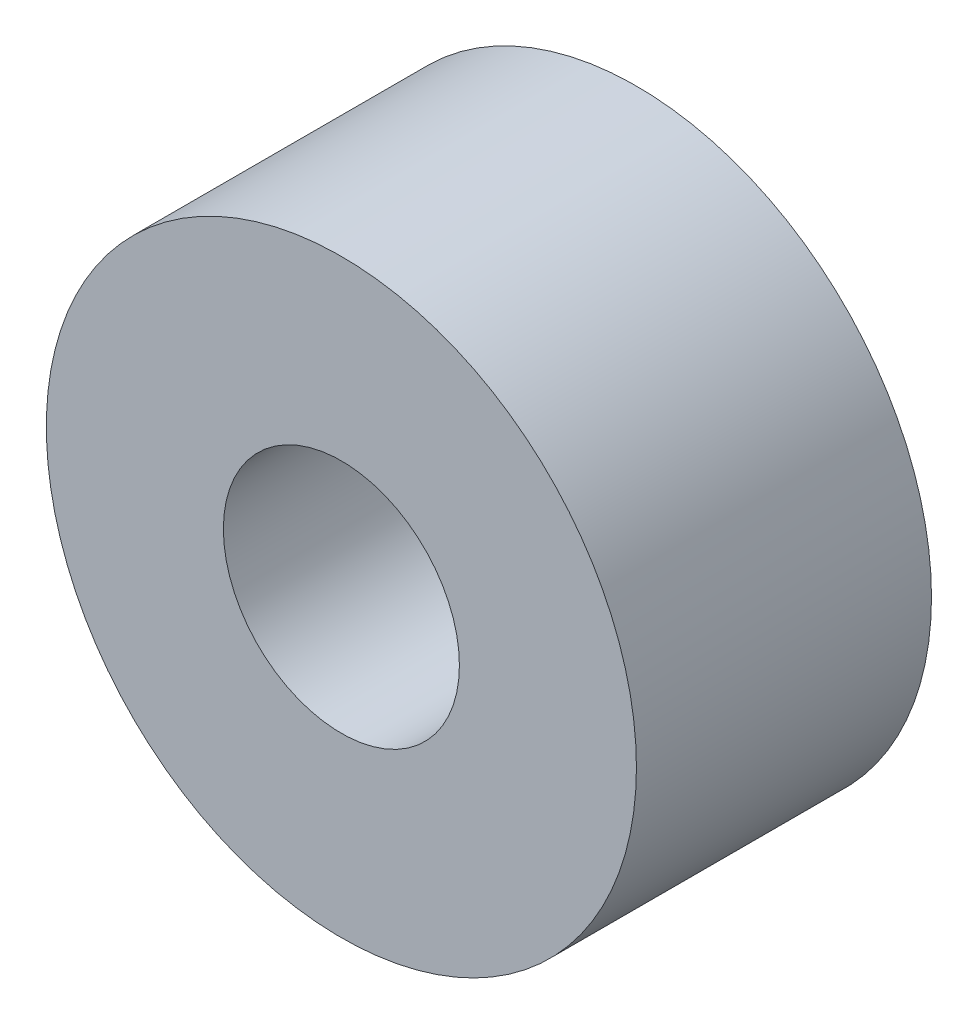
SolidWorks part; units mm, degrees
material "ABS"
ref_plane "Front Plane" through (0, 0, 0) normal (0, 0, 1) x (1, 0, 0)
ref_plane "Top Plane" through (0, 0, 0) normal (0, 1, 0) x (1, 0, 0)
ref_plane "Right Plane" through (0, 0, 0) normal (1, 0, 0) x (0, 0, -1)
sketch "Sketch1" plane through (0, 0, 0) normal (0, 0, 1) x (1, 0, 0)
  line L0 (0, 1.6) -> (0, 4) construction
  line L1 (0, -1.6) -> (0, -4) construction
  circle A0 centre (0, 0) radius 4
  circle A1 centre (0, 0) radius 1.6
  dimension "OD" = 8
  dimension "ID" = 3.2
sketch "Sketch2" plane through (0, 0, 0) normal (1, 0, 0) x (0, 0, -1)
  line L0 (-2, 1.6) -> (2, 1.6) construction
  line L1 (-2, -1.6) -> (2, -1.6) construction
  line L2 (-2, -4) -> (2, -4) construction
  line L3 (-2, 4) -> (2, 4) construction
  dimension "Length" = 4
extrude "Extrude1" add sketch "Sketch1" along normal up to vertex (2 mm away) and the other way up to vertex (2 mm away) up to point (0, 1.6, 2) other way up to point (0, 1.6, -2)
sketch "Sketch3" plane through (0, 0, 2) normal (0, 0, 1) x (1, 0, 0)
  circle A0 centre (0, 0) radius 1.6 construction
  circle A3 centre (0, 0) radius 1.6
  point P3 (-1.6, 0)
